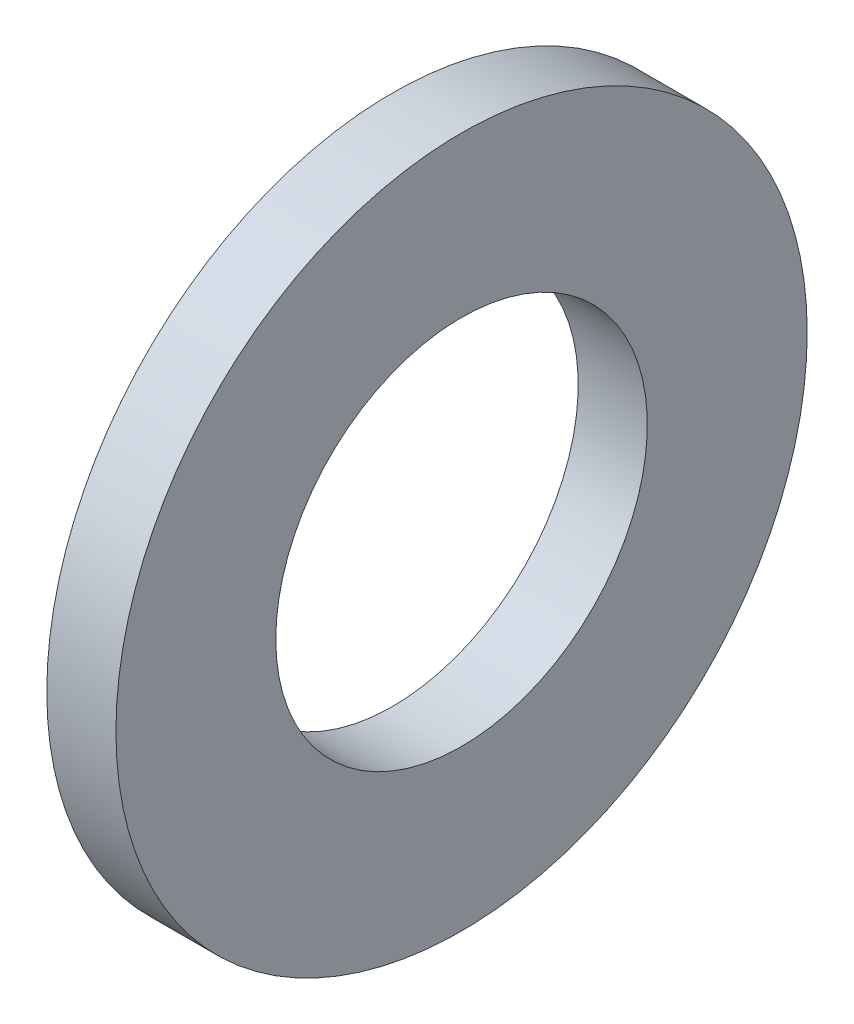
SolidWorks part; units mm, degrees
material "Acier allié"
ref_plane "Plan1" through (0, 0, 0) normal (0, 0, 1) x (1, 0, 0)
ref_plane "Plan2" through (0, 0, 0) normal (0, 1, 0) x (1, 0, 0)
ref_plane "Plan3" through (0, 0, 0) normal (1, 0, 0) x (0, 0, -1)
sketch "Esquisse1" plane through (0, 0, 0) normal (0, 1, 0) x (1, 0, 0)
  line L0 (0, 0) -> (40, 0) construction
  line L2 (0, 4) -> (0.8, 4)
  line L3 (0, 4) -> (0, 2.15)
  line L4 (0, 2.15) -> (0.8, 2.15)
  line L5 (0.8, 4) -> (0.8, 2.15)
  dimension "D1" = 2.15
  dimension "D2" = 4
  dimension "D3" = 0.8
revolve "Base-Révolution" add sketch "Esquisse1" angle 360 about L0
ref_axis "Axe1" through (-50, 0, 0) along (1, 0, 0)
